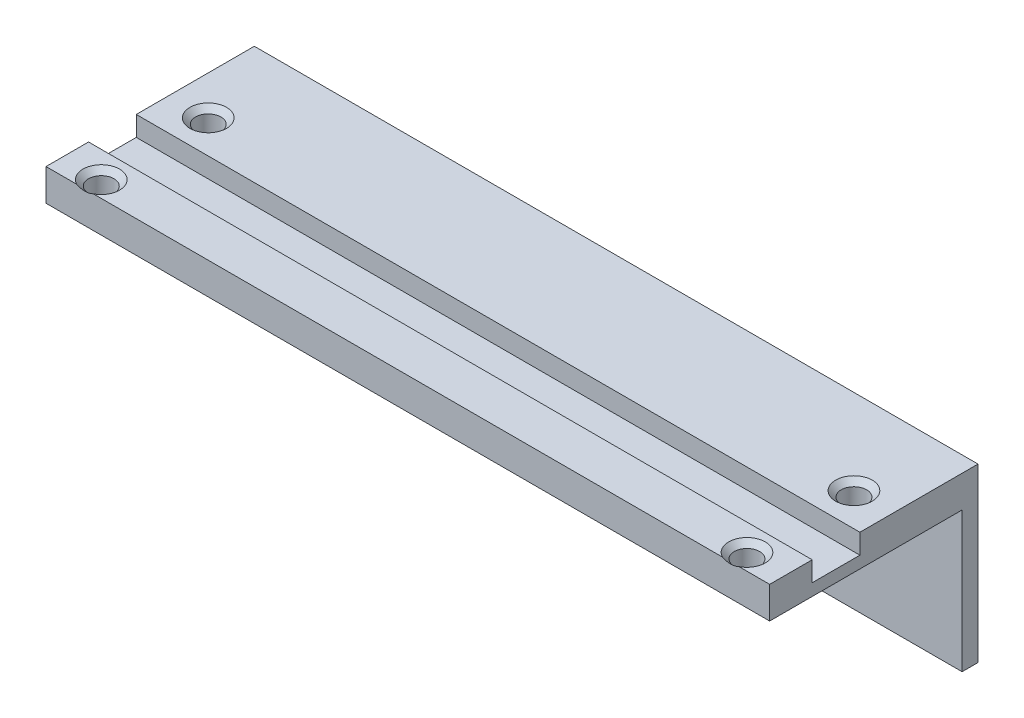
SolidWorks part; units mm, degrees
ref_plane "Front Plane" through (0, 0, 0) normal (0, 0, 1) x (1, 0, 0)
ref_plane "Top Plane" through (0, 0, 0) normal (0, 1, 0) x (1, 0, 0)
ref_plane "Right Plane" through (0, 0, 0) normal (1, 0, 0) x (0, 0, -1)
sketch "Sketch1" plane through (0, 0, 0) normal (0, 1, 0) x (1, 0, 0)
  line L5 (-45.5, 12) -> (45.5, 12)
  line L6 (-45.5, 12) -> (-45.5, -12)
  line L7 (-45.5, -12) -> (45.5, -12)
  line L8 (45.5, 12) -> (45.5, -12)
  line L9 (-45.5, 12) -> (45.5, -12) construction
  line L10 (-45.5, -12) -> (45.5, 12) construction
  point P0 (0, 0)
  dimension "D1" = 91
  dimension "D2" = 24
extrude "Boss-Extrude1" add sketch "Sketch1" along normal blind 4
sketch "Sketch2" plane through (0, 4, 0) normal (0, 1, 0) x (1, 0, 0)
  circle A0 centre (-40.6, 3.5) radius 1.6
  circle A2 centre (-40.6, -9.95) radius 1.6
  circle A3 centre (40.6, 3.5) radius 1.6
  circle A4 centre (40.6, -9.95) radius 1.6
  line B0 (-42.6, 12) -> (-42.6, -12)
  line B1 (-42.6, -12) -> (42.6, -12)
  line B2 (42.6, -12) -> (42.6, 12)
  line B3 (42.6, 12) -> (-42.6, 12)
  line B4 (-42.6, 0) -> (42.6, 0) construction
  line B5 (0, 12) -> (0, -12) construction
  arc B6 (41.75, -9.95) -> (39.45, -9.95) centre (40.6, -9.95) ccw
  arc B7 (39.45, -9.95) -> (41.75, -9.95) centre (40.6, -9.95) ccw
  arc B8 (41.75, 3.5) -> (39.45, 3.5) centre (40.6, 3.5) ccw
  arc B9 (39.45, 3.5) -> (41.75, 3.5) centre (40.6, 3.5) ccw
  arc B10 (11.65, 3.5) -> (9.35, 3.5) centre (10.5, 3.5) ccw
  arc B11 (9.35, 3.5) -> (11.65, 3.5) centre (10.5, 3.5) ccw
  arc B12 (11.65, -9.95) -> (9.35, -9.95) centre (10.5, -9.95) ccw
  arc B13 (9.35, -9.95) -> (11.65, -9.95) centre (10.5, -9.95) ccw
  arc B14 (-39.45, -9.95) -> (-41.75, -9.95) centre (-40.6, -9.95) ccw
  arc B15 (-41.75, -9.95) -> (-39.45, -9.95) centre (-40.6, -9.95) ccw
  arc B16 (-39.45, 3.5) -> (-41.75, 3.5) centre (-40.6, 3.5) ccw
  arc B17 (-41.75, 3.5) -> (-39.45, 3.5) centre (-40.6, 3.5) ccw
  arc B18 (-22.05, -3.65) -> (-20.55, -3.65) centre (-21.3, -3.65) ccw
  arc B19 (-20.55, -3.65) -> (-22.05, -3.65) centre (-21.3, -3.65) ccw
  arc B20 (-9.35, -9.95) -> (-11.65, -9.95) centre (-10.5, -9.95) ccw
  arc B21 (-11.65, -9.95) -> (-9.35, -9.95) centre (-10.5, -9.95) ccw
  arc B22 (20.55, -3.65) -> (22.05, -3.65) centre (21.3, -3.65) ccw
  arc B23 (22.05, -3.65) -> (20.55, -3.65) centre (21.3, -3.65) ccw
  arc B24 (-39.55, -3.65) -> (-38.05, -3.65) centre (-38.8, -3.65) ccw
  arc B25 (-38.05, -3.65) -> (-39.55, -3.65) centre (-38.8, -3.65) ccw
  arc B26 (38.05, -3.65) -> (39.55, -3.65) centre (38.8, -3.65) ccw
  arc B27 (39.55, -3.65) -> (38.05, -3.65) centre (38.8, -3.65) ccw
  arc B28 (-11.65, 3.5) -> (-9.35, 3.5) centre (-10.5, 3.5) ccw
  arc B29 (-9.35, 3.5) -> (-11.65, 3.5) centre (-10.5, 3.5) ccw
  dimension "D1" = 3.2
  dimension "D2" = 3.2
  dimension "D3" = 3.2
  dimension "D4" = 3.2
sketch_block_instance "Block2-2"
sketch_block "Block2"
extrude "Cut-Extrude1" cut sketch "Sketch2" against normal through all contours A2 | A4 | A0 | A3
chamfer "Chamfer1" distance 0.7 angle 45 4 edges at (-40.6, 4, 11.55) (-40.6, 4, -1.9) (40.6, 4, -1.9) (40.6, 4, 11.55)
sketch "Sketch3" plane through (0, 4, 0) normal (0, 1, 0) x (1, 0, 0)
  line L0 (-45.5, 12) -> (-45.5, -12) construction
  line L1 (-45.5, -0.65) -> (45.5, -0.65)
  line L2 (-45.5, -0.65) -> (-45.5, -6.65)
  line L3 (-45.5, -6.65) -> (45.5, -6.65)
  line L4 (45.5, -0.65) -> (45.5, -6.65)
  line L5 (45.5, -12) -> (45.5, 12) construction
  line L6 (-45.5, -3.65) -> (45.5, -3.65) construction
  line L7 (-38.8, -3.65) -> (-21.3, -3.65) construction
  line B0 (-42.6, 12) -> (-42.6, -12)
  line B1 (-42.6, -12) -> (42.6, -12)
  line B2 (42.6, -12) -> (42.6, 12)
  line B3 (42.6, 12) -> (-42.6, 12)
  line B4 (-42.6, 0) -> (42.6, 0) construction
  line B5 (0, 12) -> (0, -12) construction
  arc B6 (41.75, -9.95) -> (39.45, -9.95) centre (40.6, -9.95) ccw
  arc B7 (39.45, -9.95) -> (41.75, -9.95) centre (40.6, -9.95) ccw
  arc B8 (41.75, 3.5) -> (39.45, 3.5) centre (40.6, 3.5) ccw
  arc B9 (39.45, 3.5) -> (41.75, 3.5) centre (40.6, 3.5) ccw
  arc B10 (11.65, 3.5) -> (9.35, 3.5) centre (10.5, 3.5) ccw
  arc B11 (9.35, 3.5) -> (11.65, 3.5) centre (10.5, 3.5) ccw
  arc B12 (11.65, -9.95) -> (9.35, -9.95) centre (10.5, -9.95) ccw
  arc B13 (9.35, -9.95) -> (11.65, -9.95) centre (10.5, -9.95) ccw
  arc B14 (-39.45, -9.95) -> (-41.75, -9.95) centre (-40.6, -9.95) ccw
  arc B15 (-41.75, -9.95) -> (-39.45, -9.95) centre (-40.6, -9.95) ccw
  arc B16 (-39.45, 3.5) -> (-41.75, 3.5) centre (-40.6, 3.5) ccw
  arc B17 (-41.75, 3.5) -> (-39.45, 3.5) centre (-40.6, 3.5) ccw
  arc B18 (-22.05, -3.65) -> (-20.55, -3.65) centre (-21.3, -3.65) ccw
  arc B19 (-20.55, -3.65) -> (-22.05, -3.65) centre (-21.3, -3.65) ccw
  arc B20 (-9.35, -9.95) -> (-11.65, -9.95) centre (-10.5, -9.95) ccw
  arc B21 (-11.65, -9.95) -> (-9.35, -9.95) centre (-10.5, -9.95) ccw
  arc B22 (20.55, -3.65) -> (22.05, -3.65) centre (21.3, -3.65) ccw
  arc B23 (22.05, -3.65) -> (20.55, -3.65) centre (21.3, -3.65) ccw
  arc B24 (-39.55, -3.65) -> (-38.05, -3.65) centre (-38.8, -3.65) ccw
  arc B25 (-38.05, -3.65) -> (-39.55, -3.65) centre (-38.8, -3.65) ccw
  arc B26 (38.05, -3.65) -> (39.55, -3.65) centre (38.8, -3.65) ccw
  arc B27 (39.55, -3.65) -> (38.05, -3.65) centre (38.8, -3.65) ccw
  arc B28 (-11.65, 3.5) -> (-9.35, 3.5) centre (-10.5, 3.5) ccw
  arc B29 (-9.35, 3.5) -> (-11.65, 3.5) centre (-10.5, 3.5) ccw
  dimension "D1" = 6
sketch_block_instance "Block2-3"
extrude "Cut-Extrude2" cut sketch "Sketch3" against normal blind 2.5 contours L2 L1 L4 L3
sketch "Sketch4" plane through (0, 0, -12) normal (0, 0, -1) x (-1, 0, 0)
  line L1 (-45.5, 4) -> (45.5, 4)
  line L2 (-45.5, 4) -> (-45.5, 0)
  line L3 (-45.5, 0) -> (45.5, 0)
  line L4 (45.5, 4) -> (45.5, 0)
extrude "Boss-Extrude2" add sketch "Sketch4" along normal blind 2.2
sketch "Sketch5" plane through (0, 0, 0) normal (0, -1, 0) x (1, 0, 0)
  line L0 (45.5, 12) -> (45.5, -14.2) construction
  line L1 (-45.5, -14.2) -> (45.5, -14.2)
  line L2 (-45.5, -14.2) -> (-45.5, -12.2)
  line L3 (-45.5, -12.2) -> (45.5, -12.2)
  line L4 (45.5, -14.2) -> (45.5, -12.2)
  dimension "D1" = 2
extrude "Boss-Extrude3" add sketch "Sketch5" along normal blind 17.62
sketch "Sketch6" plane through (0, 0, -12.2) normal (0, 0, 1) x (1, 0, 0)
  line L0 (0, -17.62) -> (0, -10.12) construction
  line L1 (45.5, -17.62) -> (-45.5, -17.62) construction
  line L2 (0, -10.12) -> (21.25, -10.12) construction
  line L3 (0, -10.12) -> (-21.25, -10.12) construction
  circle A0 centre (-21.25, -10.12) radius 1.75
  circle A1 centre (0, -10.12) radius 1.75
  circle A2 centre (21.25, -10.12) radius 1.75
  dimension "D4" = 3.5
  dimension "D5" = 3.5
  dimension "D6" = 3.5
  dimension "D1" = 21.25
  dimension "D2" = 21.25
  dimension "D3" = 7.5
extrude "Cut-Extrude3" cut sketch "Sketch6" against normal through all
